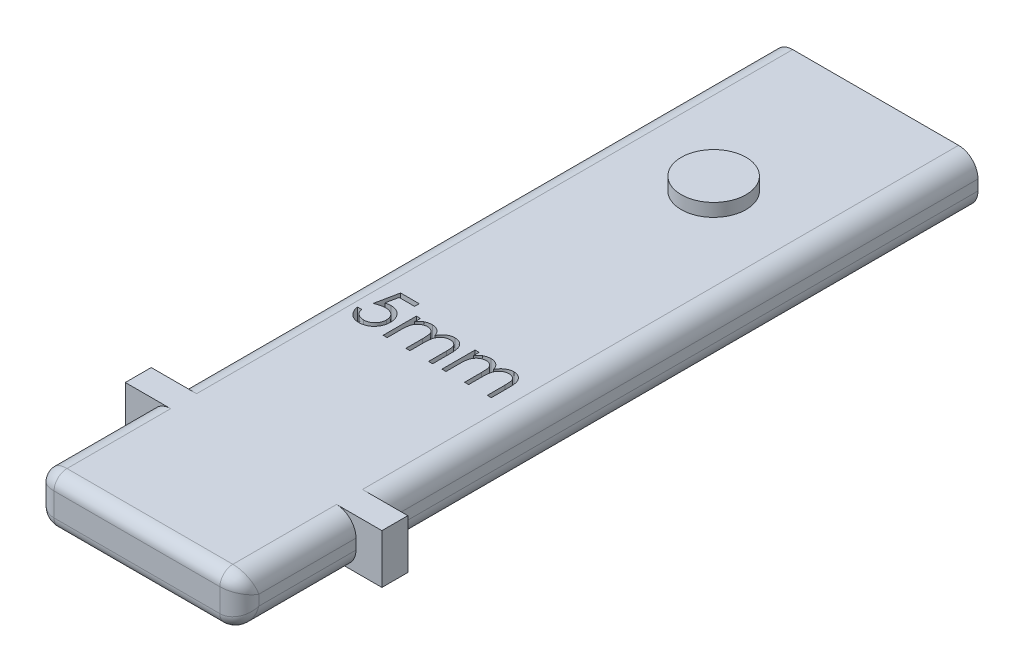
SolidWorks part; units mm, degrees
ref_plane "Front Plane" through (0, 0, 0) normal (0, 0, 1) x (1, 0, 0)
ref_plane "Top Plane" through (0, 0, 0) normal (0, 1, 0) x (1, 0, 0)
ref_plane "Right Plane" through (0, 0, 0) normal (1, 0, 0) x (0, 0, -1)
sketch "Sketch2" plane through (0, 0, 0) normal (0, 1, 0) x (1, 0, 0)
  line L1 (0, 0) -> (15.8, 0)
  line L2 (0, 0) -> (0, 57)
  line L3 (0, 57) -> (15.8, 57)
  line L4 (15.8, 0) -> (15.8, 57)
  dimension "D1" = 57
  dimension "D2" = 15.8
extrude "Boss-Extrude1" add sketch "Sketch2" along normal blind 3.8
fillet "Fillet3" radius 1 2 edges at (7.9, 0, 0) (7.9, 3.8, 0)
sketch "Sketch5" plane through (0, 3.8, 0) normal (0, 1, 0) x (1, 0, 0)
  line L0 (15.8, 57) -> (0, 57) construction
  circle A0 centre (7.9, 44.5) radius 2.5
  point P4 (7.9, 57)
  dimension "D1" = 5
  dimension "D2" = 12.5
extrude "Boss-Extrude4" add sketch "Sketch5" along normal blind 1
sketch "Sketch6" plane through (15.8, 0, 0) normal (1, 0, 0) x (0, 0, -1)
  line L0 (9, 3.8) -> (9, 0)
  line L1 (1, 3.8) -> (57, 3.8) construction
  line L2 (1, 0) -> (57, 0) construction
  line L3 (9, 0) -> (11, 0)
  line L4 (11, 0) -> (11, 3.8)
  line L5 (11, 3.8) -> (9, 3.8)
  line L6 (0, 2.8) -> (0, 1) construction
  dimension "D1" = 9
  dimension "D2" = 2
extrude "Boss-Extrude5" add sketch "Sketch6" along normal blind 2
sketch "Sketch7" plane through (0, 0, 0) normal (-1, 0, 0) x (0, 0, 1)
  line L0 (-57, 0) -> (-1, 0) construction
  line L1 (-9, 0) -> (-11, 0)
  line L2 (-9, 0) -> (-9, 3.8)
  line L3 (-9, 3.8) -> (-11, 3.8)
  line L4 (-11, 0) -> (-11, 3.8)
  line L5 (-57, 3.8) -> (-1, 3.8) construction
  line L6 (0, 2.8) -> (0, 1) construction
  dimension "D1" = 9
  dimension "D2" = 2
extrude "Boss-Extrude6" add sketch "Sketch7" along normal blind 2
fillet "Fillet4" radius 1.5 14 edges at (0, 0.2929, -0.2929) (0, 1.9, 0) (0, 3.5071, -0.2929) (15.8, 0.2929, -0.2929) (15.8, 1.9, 0) (15.8, 3.5071, -0.2929) (0, 0, -34) (0, 0, -5) (0, 3.8, -5) (0, 3.8, -34) (15.8, 0, -34) (15.8, 3.8, -34) (15.8, 0, -5) (15.8, 3.8, -5)
sketch "Sketch9" plane through (0, 3.8, 0) normal (0, 1, 0) x (1, 0, 0)
  text T0 "5mm\r\n"
extrude "Cut-Extrude1" cut sketch "Sketch9" against normal blind 5
